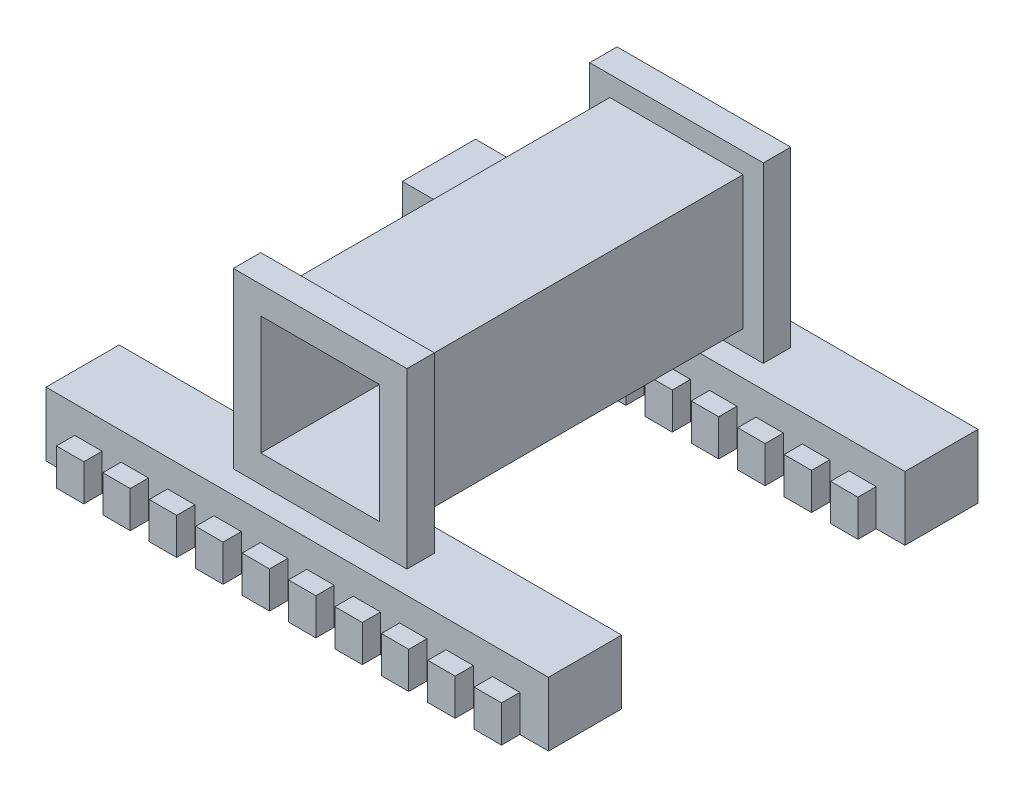
SolidWorks part; units mm, degrees
ref_plane "前视基准面" through (0, 0, 0) normal (0, 0, 1) x (1, 0, 0)
ref_plane "上视基准面" through (0, 0, 0) normal (0, 1, 0) x (1, 0, 0)
ref_plane "右视基准面" through (0, 0, 0) normal (1, 0, 0) x (0, 0, -1)
sketch "草图1" plane through (0, 0, 0) normal (0, 0, 1) x (1, 0, 0)
  line L0 (-9.5, 9.5) -> (9.5, 9.5)
  line L1 (-6.5, -6.5) -> (6.5, -6.5)
  line L2 (-6.5, -6.5) -> (-6.5, 6.5)
  line L3 (-6.5, 6.5) -> (6.5, 6.5)
  line L4 (6.5, -6.5) -> (6.5, 6.5)
  line L5 (-6.5, -6.5) -> (6.5, 6.5) construction
  line L6 (-6.5, 6.5) -> (6.5, -6.5) construction
  line L7 (9.5, -9.5) -> (9.5, 9.5)
  line L8 (-9.5, -9.5) -> (9.5, -9.5)
  line L9 (-9.5, -9.5) -> (-9.5, 9.5)
  line L10 (-7.3, 7.3) -> (7.3, 7.3)
  line L11 (7.3, -7.3) -> (7.3, 7.3)
  line L12 (-7.3, -7.3) -> (7.3, -7.3)
  line L13 (-7.3, -7.3) -> (-7.3, 7.3)
  line L15 (-27.5, -9.5) -> (27.5, -9.5)
  line L16 (-27.5, -9.5) -> (-27.5, -16.5)
  line L17 (-27.5, -16.5) -> (27.5, -16.5)
  line L18 (27.5, -9.5) -> (27.5, -16.5)
  point P0 (0, 0)
  dimension "D1" = 3
  dimension "D2" = 0.8
extrude "凸台-拉伸1" add sketch "草图1" along normal mid plane 42 contours L18 L15 L8 L16 L17 | L9 L8 L7 L0 L12 L13 L10 L11 | L13 L10 L11 L12 region at (0, 9.2313, 0) region at (0, -13, 0)
extrude "切除-拉伸1" cut sketch "草图1<3>" against normal mid plane 42 contours L2 L3 L4 L1
sketch "草图1<3>" plane through (0, 0, 0) normal (0, 0, 1) x (1, 0, 0) same geometry as "草图1"
sketch "草图2" plane through (0, 0, 0) normal (1, 0, 0) x (0, 0, -1)
  line L0 (21, -16.5) -> (21, -9.5) construction
  line L1 (21, -9.5) -> (-21, -9.5) construction
  line L2 (-21, -9.5) -> (-21, -16.5) construction
  line L3 (-21, -16.5) -> (21, -16.5) construction
  line L4 (21, -9.5) -> (21, 9.5) construction
  line L5 (21, 9.5) -> (-21, 9.5) construction
  line L6 (-21, 9.5) -> (-21, -9.5) construction
  line L7 (-21, -9.5) -> (21, -9.5) construction
  line L8 (21, -16.5) -> (21, -9.5)
  line L9 (21, -9.5) -> (-21, -9.5)
  line L10 (-21, -9.5) -> (-21, -16.5)
  line L11 (-21, -16.5) -> (21, -16.5)
  line L12 (21, -9.5) -> (21, 9.5)
  line L13 (21, 9.5) -> (-21, 9.5)
  line L14 (-21, 9.5) -> (-21, -9.5)
  line L15 (-21, -9.5) -> (21, -9.5)
extrude "切除-拉伸6" cut sketch "草图1<12>" against normal mid plane 36 contours L1 L4 L3 L2 | L9 L0 L7 L8 | L13 L10 L11 L12 region at (0, 0, 0)
sketch "草图1<12>" plane through (0, 0, 0) normal (0, 0, 1) x (1, 0, 0) same geometry as "草图1"
extrude "切除-拉伸7" cut sketch "草图1<13>" against normal mid plane 29 contours L18 L15 L8 L16 L17 region at (0, -13, 0)
sketch "草图1<13>" plane through (0, 0, 0) normal (0, 0, 1) x (1, 0, 0) same geometry as "草图1"
sketch "草图4" plane through (0, 0, 0) normal (1, 0, 0) x (0, 0, -1)
  line L0 (-21, -9.5) -> (-14.5, -9.5) construction
  line L1 (-14.5, -9.5) -> (-14.5, -16.5) construction
  line L2 (-14.5, -16.5) -> (-21, -16.5) construction
  line L3 (-21, -16.5) -> (-21, -9.5) construction
  line L4 (-18, 9.5) -> (-18, -9.5) construction
  line L5 (-18, -9.5) -> (-21, -9.5) construction
  line L6 (-21, -9.5) -> (-21, 9.5) construction
  line L7 (-21, 9.5) -> (-18, 9.5) construction
  line L8 (-18, -7.3) -> (-18, 7.3) construction
  line L9 (-18, 7.3) -> (18, 7.3) construction
  line L10 (18, 7.3) -> (18, -7.3) construction
  line L11 (18, -7.3) -> (-18, -7.3) construction
  line L12 (21, -9.5) -> (18, -9.5) construction
  line L13 (18, -9.5) -> (18, 9.5) construction
  line L14 (18, 9.5) -> (21, 9.5) construction
  line L15 (21, 9.5) -> (21, -9.5) construction
  line L16 (14.5, -16.5) -> (14.5, -9.5) construction
  line L17 (14.5, -9.5) -> (21, -9.5) construction
  line L18 (21, -9.5) -> (21, -16.5) construction
  line L19 (21, -16.5) -> (14.5, -16.5) construction
  line L20 (-21, -9.5) -> (-14.5, -9.5)
  line L21 (-14.5, -9.5) -> (-14.5, -16.5)
  line L22 (-14.5, -16.5) -> (-21, -16.5)
  line L23 (-21, -16.5) -> (-21, -9.5)
  line L24 (-18, 9.5) -> (-18, -9.5)
  line L25 (-18, -9.5) -> (-21, -9.5)
  line L26 (-21, -9.5) -> (-21, 9.5)
  line L27 (-21, 9.5) -> (-18, 9.5)
  line L28 (-18, -7.3) -> (-18, 7.3)
  line L29 (-18, 7.3) -> (18, 7.3)
  line L30 (18, 7.3) -> (18, -7.3)
  line L31 (18, -7.3) -> (-18, -7.3)
  line L32 (21, -9.5) -> (18, -9.5)
  line L33 (18, -9.5) -> (18, 9.5)
  line L34 (18, 9.5) -> (21, 9.5)
  line L35 (21, 9.5) -> (21, -9.5)
  line L36 (14.5, -16.5) -> (14.5, -9.5)
  line L37 (14.5, -9.5) -> (21, -9.5)
  line L38 (21, -9.5) -> (21, -16.5)
  line L39 (21, -16.5) -> (14.5, -16.5)
  line L40 (21, -9.5) -> (24.5, -9.5)
  line L41 (24.5, -9.5) -> (24.5, -16.5)
  line L42 (24.5, -16.5) -> (21, -16.5)
  line L43 (-21, -16.5) -> (-24.5049, -16.5)
  line L44 (-24.5049, -16.5) -> (-24.5049, -9.5)
  line L45 (-24.5049, -9.5) -> (-21, -9.5)
extrude "凸台-拉伸2" add sketch "草图4" along normal mid plane 55 contours L42 L41 L40 L38 | L45 L44 L43 L23 region at (0, -13, 22.7525) region at (0, -13, -22.75)
sketch "草图5" plane through (0, 0, -24.5) normal (0, 0, -1) x (-1, 0, 0)
  line L4 (27.5, -16.5) -> (27.5, -9.5)
  line L5 (27.5, -9.5) -> (-27.5, -9.5)
  line L6 (-27.5, -9.5) -> (-27.5, -16.5)
  line L7 (-27.5, -16.5) -> (27.5, -16.5)
  line L8 (27.5, -16.5) -> (27.5, -9.5)
  line L9 (27.5, -9.5) -> (-27.5, -9.5)
  line L10 (-27.5, -9.5) -> (-27.5, -16.5)
  line L12 (-9.5, -9.5) -> (9.5, -9.5)
  line L13 (-9.5, 9.5) -> (-9.5, -9.5)
  line L14 (9.5, 9.5) -> (-9.5, 9.5)
  line L15 (9.5, -9.5) -> (9.5, 9.5)
  line L16 (-9.5, -9.5) -> (9.5, -9.5)
  line L17 (-9.5, 9.5) -> (-9.5, -9.5)
  line L18 (9.5, 9.5) -> (-9.5, 9.5)
  line L19 (9.5, -9.5) -> (9.5, 9.5)
  line L24 (-27.5, -16.5) -> (27.5, -16.5) construction
  line L37 (22.8593, -16.5) -> (27.5, -16.5)
  line L50 (-21.36, -16.5) -> (-24.36, -16.5)
  line L55 (-11.187, -12.5036) -> (-14.213, -12.5036)
  line L56 (-11.187, -12.5036) -> (-11.187, -16.5)
  line L61 (-6.12, -16.5) -> (-9.12, -16.5)
  line L62 (-6.12, -16.5) -> (-6.12, -12.5036)
  line L68 (-1.04, -16.4978) -> (-4.04, -16.4978)
  line L86 (9.12, -16.5) -> (6.12, -16.5)
  line L91 (9.12, -16.5) -> (9.12, -12.5)
  line L92 (9.12, -12.5) -> (6.12, -12.5)
  line L97 (6.12, -16.5) -> (6.12, -12.5)
  line L98 (9.12, -16.5) -> (6.12, -12.5) construction
  line L103 (-21.36, -16.5) -> (-21.36, -12.5036)
  line L104 (-21.36, -12.5036) -> (-24.36, -12.5036)
  line L105 (-24.36, -16.5) -> (-24.36, -12.5036)
  line L106 (-21.36, -16.5) -> (-24.36, -12.5036) construction
  line L107 (-21.36, -12.5036) -> (-24.36, -16.5) construction
  line L108 (-19.28, -16.5) -> (-16.28, -16.5)
  line L109 (-19.28, -16.5) -> (-19.28, -12.5036)
  line L110 (-19.28, -12.5036) -> (-16.28, -12.5036)
  line L111 (-16.28, -16.5) -> (-16.28, -12.5036)
  line L112 (-19.28, -16.5) -> (-16.28, -12.5036) construction
  line L113 (-19.28, -12.5036) -> (-16.28, -16.5) construction
  line L114 (-11.187, -16.5) -> (-14.213, -16.5)
  line L115 (-14.213, -12.5036) -> (-14.213, -16.5)
  line L116 (-11.187, -12.5036) -> (-14.213, -16.5) construction
  line L117 (-11.187, -16.5) -> (-14.213, -12.5036) construction
  line L118 (-6.12, -12.5036) -> (-9.12, -12.5036)
  line L119 (-9.12, -16.5) -> (-9.12, -12.5036)
  line L120 (-6.12, -16.5) -> (-9.12, -12.5036) construction
  line L121 (-6.12, -12.5036) -> (-9.12, -16.5) construction
  line L122 (-1.04, -16.4978) -> (-1.04, -12.4978)
  line L123 (-1.04, -12.4978) -> (-4.04, -12.4978)
  line L124 (-4.04, -16.4978) -> (-4.04, -12.4978)
  line L125 (-1.04, -16.4978) -> (-4.04, -12.4978) construction
  line L126 (-1.04, -12.4978) -> (-4.04, -16.4978) construction
  line L128 (9.12, -12.5) -> (6.12, -16.5) construction
  line L129 (4.04, -16.5) -> (1.038, -16.5)
  line L130 (4.04, -16.5) -> (4.04, -12.4956)
  line L131 (4.04, -12.4956) -> (1.038, -12.4956)
  line L132 (1.038, -16.5) -> (1.038, -12.4956)
  line L133 (4.04, -16.5) -> (1.038, -12.4956) construction
  line L134 (4.04, -12.4956) -> (1.038, -16.5) construction
  line L135 (14.2014, -16.5) -> (11.1986, -16.5)
  line L136 (14.2014, -16.5) -> (14.2014, -12.5)
  line L137 (14.2014, -12.5) -> (11.1986, -12.5)
  line L138 (11.1986, -16.5) -> (11.1986, -12.5)
  line L139 (14.2014, -16.5) -> (11.1986, -12.5) construction
  line L140 (14.2014, -12.5) -> (11.1986, -16.5) construction
  line L141 (19.28, -16.4935) -> (16.28, -16.4935)
  line L142 (19.28, -16.4935) -> (19.28, -12.4935)
  line L143 (19.28, -12.4935) -> (16.28, -12.4935)
  line L144 (16.28, -16.4935) -> (16.28, -12.4935)
  line L145 (19.28, -16.4935) -> (16.28, -12.4935) construction
  line L146 (19.28, -12.4935) -> (16.28, -16.4935) construction
  line L151 (24.3586, -16.5) -> (21.36, -16.5)
  line L152 (24.3586, -16.5) -> (24.3586, -12.487)
  line L153 (24.3586, -12.487) -> (21.36, -12.487)
  line L154 (21.36, -16.5) -> (21.36, -12.487)
  line L155 (24.3586, -16.5) -> (21.36, -12.487) construction
  line L156 (24.3586, -12.487) -> (21.36, -16.5) construction
  point P6 (-22.86, -14.5018)
  point P33 (-17.78, -14.5018)
  point P35 (-17.78, -14.5018)
  point P39 (-12.7, -14.5018)
  point P40 (-12.7, -14.5018)
  point P45 (-7.62, -14.5018)
  point P50 (-2.54, -14.4978)
  point P55 (2.539, -14.4978)
  point P60 (7.62, -14.5)
  point P65 (12.7, -14.5)
  point P70 (17.78, -14.4935)
  point P75 (22.8593, -14.4935)
  dimension "D1" = 0
  dimension "D2" = 0
sketch "草图10" plane through (27.5, 0, 0) normal (1, 0, 0) x (0, 0, -1)
  line L0 (-24.5049, -16.5) -> (-25.5049, -16.5)
  line L1 (-24.5049, -16.5) -> (-24.5049, -9.5)
  line L2 (-24.5049, -9.5) -> (-25.5049, -9.5)
  line L3 (-25.5049, -9.5) -> (-25.5049, -16.5)
  line L4 (-14.5, -16.5) -> (-13.5, -16.5)
  line L5 (-13.5, -16.5) -> (-13.5, -9.5)
  line L6 (-13.5, -9.5) -> (-14.5, -9.5)
  line L7 (-14.5, -9.5) -> (-14.5, -16.5)
  line L8 (14.4975, -9.5) -> (14.4975, -16.5)
  line L11 (-0.0012, -16.5) -> (-0.0012, -9.5)
  line L12 (13.4975, -9.5) -> (14.4975, -9.5)
  line L13 (13.4975, -16.5) -> (13.4975, -9.5)
  line L14 (14.4975, -16.5) -> (13.4975, -16.5)
  line L15 (25.5025, -9.5) -> (25.5025, -16.5)
  line L16 (24.5025, -9.5) -> (25.5025, -9.5)
  line L17 (24.5025, -16.5) -> (24.5025, -9.5)
  line L18 (24.5025, -16.5) -> (25.5025, -16.5)
extrude "凸台-拉伸4" add sketch "草图10" against normal blind 55 contours L7 L4 L5 L6 | L3 L0 L1 L2
sketch "草图14" plane through (27.5, 0, 0) normal (1, 0, 0) x (0, 0, -1)
  line L0 (14.5, -9.5) -> (13.5, -9.5)
  line L1 (14.5, -16.5) -> (13.5, -16.5)
  line L2 (13.5, -16.5) -> (13.5, -9.5)
  line L3 (24.5, -9.5) -> (25.5, -9.5)
  line L4 (24.5, -16.5) -> (25.5, -16.5)
  line L5 (25.5, -16.5) -> (25.5, -9.5)
  line L6 (24.5, -9.5) -> (24.5, -16.5)
  line L7 (14.5, -9.5) -> (14.5, -16.5)
extrude "凸台-拉伸6" add sketch "草图14" against normal blind 55
sketch "草图15" plane through (0, 0, -25.5) normal (0, 0, -1) x (-1, 0, 0)
  line L0 (-27.5, -16.5) -> (-22.86, -16.5)
  line L1 (27.5, -16.5) -> (-27.5, -16.5) construction
  line L2 (-22.86, -16.5) -> (-22.86, -12.5)
  line L4 (-17.78, -12.5) -> (-17.78, -16.5)
  line L5 (-11.2, -16.5) -> (-14.2, -16.5)
  line L6 (-12.7, -16.5) -> (-12.7, -12.5)
  line L7 (-11.2, -16.5) -> (-11.2, -12.5)
  line L8 (-7.62, -12.5) -> (-7.62, -16.5)
  line L9 (-11.2, -12.5) -> (-14.2, -12.5)
  line L10 (-2.54, -16.5) -> (-2.54, -12.5)
  line L11 (-1.04, -16.5) -> (-4.04, -16.5)
  line L12 (2.54, -12.5) -> (2.54, -16.5)
  line L13 (-1.04, -16.5) -> (-1.04, -12.5)
  line L14 (7.62, -16.5) -> (7.62, -12.5)
  line L15 (6.12, -16.5) -> (9.12, -16.5)
  line L16 (12.7, -12.5) -> (12.7, -16.5)
  line L17 (6.12, -16.5) -> (6.12, -12.5)
  line L18 (17.78, -16.5) -> (17.78, -12.5)
  line L19 (6.12, -12.5) -> (9.12, -12.5)
  line L20 (22.86, -12.5) -> (22.86, -16.5)
  line L21 (24.36, -16.5) -> (21.36, -16.5)
  line L31 (24.36, -16.5) -> (24.36, -12.5)
  line L32 (24.36, -12.5) -> (21.36, -12.5)
  line L37 (9.12, -16.5) -> (9.12, -12.5)
  line L38 (6.12, -16.5) -> (9.12, -12.5) construction
  line L39 (-19.28, -16.5) -> (-16.28, -16.5)
  line L48 (-21.36, -16.5) -> (-24.36, -16.5)
  line L49 (-21.36, -16.5) -> (-21.36, -12.5)
  line L50 (-21.36, -12.5) -> (-24.36, -12.5)
  line L51 (-24.36, -16.5) -> (-24.36, -12.5)
  line L52 (-21.36, -16.5) -> (-24.36, -12.5) construction
  line L53 (-21.36, -12.5) -> (-24.36, -16.5) construction
  line L58 (-19.28, -16.5) -> (-19.28, -12.5)
  line L59 (-19.28, -12.5) -> (-16.28, -12.5)
  line L60 (-16.28, -16.5) -> (-16.28, -12.5)
  line L61 (-19.28, -16.5) -> (-16.28, -12.5) construction
  line L62 (-19.28, -12.5) -> (-16.28, -16.5) construction
  line L67 (-14.2, -16.5) -> (-14.2, -12.5)
  line L68 (-11.2, -16.5) -> (-14.2, -12.5) construction
  line L69 (-11.2, -12.5) -> (-14.2, -16.5) construction
  line L70 (-9.12, -16.5) -> (-6.12, -16.5)
  line L71 (-9.12, -16.5) -> (-9.12, -12.5)
  line L72 (-9.12, -12.5) -> (-6.12, -12.5)
  line L73 (-6.12, -16.5) -> (-6.12, -12.5)
  line L74 (-9.12, -16.5) -> (-6.12, -12.5) construction
  line L75 (-9.12, -12.5) -> (-6.12, -16.5) construction
  line L76 (-1.04, -12.5) -> (-4.04, -12.5)
  line L77 (-4.04, -16.5) -> (-4.04, -12.5)
  line L78 (-1.04, -16.5) -> (-4.04, -12.5) construction
  line L79 (-1.04, -12.5) -> (-4.04, -16.5) construction
  line L80 (4.04, -16.5) -> (1.04, -16.5)
  line L81 (4.04, -16.5) -> (4.04, -12.5)
  line L82 (4.04, -12.5) -> (1.04, -12.5)
  line L83 (1.04, -16.5) -> (1.04, -12.5)
  line L84 (4.04, -16.5) -> (1.04, -12.5) construction
  line L85 (4.04, -12.5) -> (1.04, -16.5) construction
  line L86 (6.12, -12.5) -> (9.12, -16.5) construction
  line L87 (11.2, -16.5) -> (14.2, -16.5)
  line L88 (11.2, -16.5) -> (11.2, -12.5)
  line L89 (11.2, -12.5) -> (14.2, -12.5)
  line L90 (14.2, -16.5) -> (14.2, -12.5)
  line L91 (11.2, -16.5) -> (14.2, -12.5) construction
  line L92 (11.2, -12.5) -> (14.2, -16.5) construction
  line L93 (16.28, -16.5) -> (19.28, -16.5)
  line L94 (16.28, -16.5) -> (16.28, -12.5)
  line L95 (16.28, -12.5) -> (19.28, -12.5)
  line L96 (19.28, -16.5) -> (19.28, -12.5)
  line L97 (16.28, -16.5) -> (19.28, -12.5) construction
  line L98 (16.28, -12.5) -> (19.28, -16.5) construction
  line L99 (21.36, -16.5) -> (21.36, -12.5)
  line L100 (24.36, -16.5) -> (21.36, -12.5) construction
  line L101 (24.36, -12.5) -> (21.36, -16.5) construction
  point P17 (22.86, -14.5)
  point P25 (22.86, -14.5)
  point P26 (22.86, -14.5)
  point P31 (17.78, -14.5)
  point P32 (7.62, -14.5)
  point P36 (-22.86, -14.5)
  point P41 (-17.78, -14.5)
  point P42 (-17.78, -14.5)
  point P47 (-12.7, -14.5)
  point P52 (-7.62, -14.5)
  point P57 (-2.54, -14.5)
  point P62 (2.54, -14.5)
  point P68 (12.7, -14.5)
  point P73 (17.78, -14.5)
  line M64 (-27.5, -9.5) -> (-27.5, -16.5)
  line M65 (-27.5, -16.5) -> (27.5, -16.5)
  line M66 (27.5, -16.5) -> (27.5, -9.5)
  line M67 (27.5, -9.5) -> (-27.5, -9.5)
extrude "切除-拉伸22" cut sketch "草图15" against normal blind 2 contours L99 L32 L31 L51 L50 L49 L58 L59 L60 L67 L9 L7 L71 L72 L73 L77 L76 L13 L83 L82 L81 L17 L19 L37 L88 L89 L90 L94 M65 M66 M67 M64 region at (0, -12.3208, -25.5)
sketch "草图20" plane through (0, 0, 13.5) normal (0, 0, -1) x (-1, 0, 0)
  line L0 (21.36, -16.5) -> (24.36, -16.5) construction
  line L1 (24.36, -16.5) -> (24.36, -12.5) construction
  line L2 (24.36, -12.5) -> (21.36, -12.5) construction
  line L3 (21.36, -12.5) -> (21.36, -16.5) construction
  line L4 (-27.5, -9.5) -> (-27.5, -16.5)
  line L5 (-27.5, -16.5) -> (27.5, -16.5)
  line L6 (27.5, -16.5) -> (27.5, -9.5)
  line L7 (27.5, -9.5) -> (-27.5, -9.5)
  line L8 (-27.5, -9.5) -> (-27.5, -16.5)
  line L9 (-27.5, -16.5) -> (27.5, -16.5)
  line L10 (27.5, -16.5) -> (27.5, -9.5)
  line L11 (27.5, -9.5) -> (-27.5, -9.5)
  line L12 (16.28, -16.5) -> (19.28, -16.5) construction
  line L13 (19.28, -16.5) -> (19.28, -12.5) construction
  line L14 (19.28, -12.5) -> (16.28, -12.5) construction
  line L15 (16.28, -12.5) -> (16.28, -16.5) construction
  line L16 (11.2, -16.5) -> (14.2, -16.5) construction
  line L17 (14.2, -16.5) -> (14.2, -12.5) construction
  line L18 (14.2, -12.5) -> (11.2, -12.5) construction
  line L19 (11.2, -12.5) -> (11.2, -16.5) construction
  line L20 (6.12, -16.5) -> (9.12, -16.5) construction
  line L21 (9.12, -16.5) -> (9.12, -12.5) construction
  line L22 (9.12, -12.5) -> (6.12, -12.5) construction
  line L23 (6.12, -12.5) -> (6.12, -16.5) construction
  line L24 (1.04, -16.5) -> (4.04, -16.5) construction
  line L25 (4.04, -16.5) -> (4.04, -12.5) construction
  line L26 (4.04, -12.5) -> (1.04, -12.5) construction
  line L27 (1.04, -12.5) -> (1.04, -16.5) construction
  line L28 (-4.04, -16.5) -> (-1.04, -16.5) construction
  line L29 (-1.04, -16.5) -> (-1.04, -12.5) construction
  line L30 (-1.04, -12.5) -> (-4.04, -12.5) construction
  line L31 (-4.04, -12.5) -> (-4.04, -16.5) construction
  line L32 (-9.12, -16.5) -> (-6.12, -16.5) construction
  line L33 (-6.12, -16.5) -> (-6.12, -12.5) construction
  line L34 (-6.12, -12.5) -> (-9.12, -12.5) construction
  line L35 (-9.12, -12.5) -> (-9.12, -16.5) construction
  line L36 (-14.2, -16.5) -> (-11.2, -16.5) construction
  line L37 (-11.2, -16.5) -> (-11.2, -12.5) construction
  line L38 (-11.2, -12.5) -> (-14.2, -12.5) construction
  line L39 (-14.2, -12.5) -> (-14.2, -16.5) construction
  line L40 (-19.28, -16.5) -> (-16.28, -16.5) construction
  line L41 (-16.28, -16.5) -> (-16.28, -12.5) construction
  line L42 (-16.28, -12.5) -> (-19.28, -12.5) construction
  line L43 (-19.28, -12.5) -> (-19.28, -16.5) construction
  line L44 (-24.36, -16.5) -> (-21.36, -16.5) construction
  line L45 (-21.36, -16.5) -> (-21.36, -12.5) construction
  line L46 (-21.36, -12.5) -> (-24.36, -12.5) construction
  line L47 (-24.36, -12.5) -> (-24.36, -16.5) construction
  line L48 (21.36, -16.5) -> (24.36, -16.5)
  line L49 (24.36, -16.5) -> (24.36, -12.5)
  line L50 (24.36, -12.5) -> (21.36, -12.5)
  line L51 (21.36, -12.5) -> (21.36, -16.5)
  line L52 (16.28, -16.5) -> (19.28, -16.5)
  line L53 (19.28, -16.5) -> (19.28, -12.5)
  line L54 (19.28, -12.5) -> (16.28, -12.5)
  line L55 (16.28, -12.5) -> (16.28, -16.5)
  line L56 (11.2, -16.5) -> (14.2, -16.5)
  line L57 (14.2, -16.5) -> (14.2, -12.5)
  line L58 (14.2, -12.5) -> (11.2, -12.5)
  line L59 (11.2, -12.5) -> (11.2, -16.5)
  line L60 (6.12, -16.5) -> (9.12, -16.5)
  line L61 (9.12, -16.5) -> (9.12, -12.5)
  line L62 (9.12, -12.5) -> (6.12, -12.5)
  line L63 (6.12, -12.5) -> (6.12, -16.5)
  line L64 (1.04, -16.5) -> (4.04, -16.5)
  line L65 (4.04, -16.5) -> (4.04, -12.5)
  line L66 (4.04, -12.5) -> (1.04, -12.5)
  line L67 (1.04, -12.5) -> (1.04, -16.5)
  line L68 (-4.04, -16.5) -> (-1.04, -16.5)
  line L69 (-1.04, -16.5) -> (-1.04, -12.5)
  line L70 (-1.04, -12.5) -> (-4.04, -12.5)
  line L71 (-4.04, -12.5) -> (-4.04, -16.5)
  line L72 (-9.12, -16.5) -> (-6.12, -16.5)
  line L73 (-6.12, -16.5) -> (-6.12, -12.5)
  line L74 (-6.12, -12.5) -> (-9.12, -12.5)
  line L75 (-9.12, -12.5) -> (-9.12, -16.5)
  line L76 (-14.2, -16.5) -> (-11.2, -16.5)
  line L77 (-11.2, -16.5) -> (-11.2, -12.5)
  line L78 (-11.2, -12.5) -> (-14.2, -12.5)
  line L79 (-14.2, -12.5) -> (-14.2, -16.5)
  line L80 (-19.28, -16.5) -> (-16.28, -16.5)
  line L81 (-16.28, -16.5) -> (-16.28, -12.5)
  line L82 (-16.28, -12.5) -> (-19.28, -12.5)
  line L83 (-19.28, -12.5) -> (-19.28, -16.5)
  line L84 (-24.36, -16.5) -> (-21.36, -16.5)
  line L85 (-21.36, -16.5) -> (-21.36, -12.5)
  line L86 (-21.36, -12.5) -> (-24.36, -12.5)
  line L87 (-24.36, -12.5) -> (-24.36, -16.5)
  line M5 (-27.5, -9.5) -> (-27.5, -16.5)
  line M6 (-27.5, -16.5) -> (27.5, -16.5)
  line M7 (27.5, -16.5) -> (27.5, -9.5)
  line M8 (27.5, -9.5) -> (-27.5, -9.5)
  dimension "D1" = 0
extrude "切除-拉伸23" cut sketch "草图20" against normal blind 2 contours L87 L86 L85 L83 L82 L81 L79 L78 L77 L75 L74 L73 L71 L70 L69 L67 L66 L65 L63 L62 L61 L59 L58 L57 L55 L54 L53 L51 L50 L49 M6 M7 M8 M5 region at (0, -12.3208, 13.5)
sketch "草图21" plane through (0, 0, -13.5) normal (0, 0, 1) x (1, 0, 0)
  line L0 (-21.36, -16.5) -> (-24.36, -16.5) construction
  line L1 (-24.36, -16.5) -> (-24.36, -12.5) construction
  line L2 (-24.36, -12.5) -> (-21.36, -12.5) construction
  line L3 (-21.36, -12.5) -> (-21.36, -16.5) construction
  line L4 (27.5, -16.5) -> (27.5, -9.5)
  line L5 (27.5, -9.5) -> (-27.5, -9.5)
  line L6 (-27.5, -9.5) -> (-27.5, -16.5)
  line L7 (-27.5, -16.5) -> (27.5, -16.5)
  line L8 (27.5, -16.5) -> (27.5, -9.5)
  line L9 (27.5, -9.5) -> (-27.5, -9.5)
  line L10 (-27.5, -9.5) -> (-27.5, -16.5)
  line L11 (-27.5, -16.5) -> (27.5, -16.5)
  line L12 (-16.28, -16.5) -> (-19.28, -16.5) construction
  line L13 (-19.28, -16.5) -> (-19.28, -12.5) construction
  line L14 (-19.28, -12.5) -> (-16.28, -12.5) construction
  line L15 (-16.28, -12.5) -> (-16.28, -16.5) construction
  line L16 (-11.2, -16.5) -> (-14.2, -16.5) construction
  line L17 (-14.2, -16.5) -> (-14.2, -12.5) construction
  line L18 (-14.2, -12.5) -> (-11.2, -12.5) construction
  line L19 (-11.2, -12.5) -> (-11.2, -16.5) construction
  line L20 (-6.12, -16.5) -> (-9.12, -16.5) construction
  line L21 (-9.12, -16.5) -> (-9.12, -12.5) construction
  line L22 (-9.12, -12.5) -> (-6.12, -12.5) construction
  line L23 (-6.12, -12.5) -> (-6.12, -16.5) construction
  line L24 (-1.04, -16.5) -> (-4.04, -16.5) construction
  line L25 (-4.04, -16.5) -> (-4.04, -12.5) construction
  line L26 (-4.04, -12.5) -> (-1.04, -12.5) construction
  line L27 (-1.04, -12.5) -> (-1.04, -16.5) construction
  line L28 (4.04, -16.5) -> (1.04, -16.5) construction
  line L29 (1.04, -16.5) -> (1.04, -12.5) construction
  line L30 (1.04, -12.5) -> (4.04, -12.5) construction
  line L31 (4.04, -12.5) -> (4.04, -16.5) construction
  line L32 (9.12, -16.5) -> (6.12, -16.5) construction
  line L33 (6.12, -16.5) -> (6.12, -12.5) construction
  line L34 (6.12, -12.5) -> (9.12, -12.5) construction
  line L35 (9.12, -12.5) -> (9.12, -16.5) construction
  line L36 (21.36, -12.5) -> (24.36, -12.5) construction
  line L37 (24.36, -12.5) -> (24.36, -16.5) construction
  line L38 (24.36, -16.5) -> (21.36, -16.5) construction
  line L39 (21.36, -16.5) -> (21.36, -12.5) construction
  line L40 (14.2, -16.5) -> (11.2, -16.5) construction
  line L41 (11.2, -16.5) -> (11.2, -12.5) construction
  line L42 (11.2, -12.5) -> (14.2, -12.5) construction
  line L43 (14.2, -12.5) -> (14.2, -16.5) construction
  line L44 (19.28, -16.5) -> (16.28, -16.5) construction
  line L45 (16.28, -16.5) -> (16.28, -12.5) construction
  line L46 (16.28, -12.5) -> (19.28, -12.5) construction
  line L47 (19.28, -12.5) -> (19.28, -16.5) construction
  line L48 (-21.36, -16.5) -> (-24.36, -16.5)
  line L49 (-24.36, -16.5) -> (-24.36, -12.5)
  line L50 (-24.36, -12.5) -> (-21.36, -12.5)
  line L51 (-21.36, -12.5) -> (-21.36, -16.5)
  line L52 (-16.28, -16.5) -> (-19.28, -16.5)
  line L53 (-19.28, -16.5) -> (-19.28, -12.5)
  line L54 (-19.28, -12.5) -> (-16.28, -12.5)
  line L55 (-16.28, -12.5) -> (-16.28, -16.5)
  line L56 (-11.2, -16.5) -> (-14.2, -16.5)
  line L57 (-14.2, -16.5) -> (-14.2, -12.5)
  line L58 (-14.2, -12.5) -> (-11.2, -12.5)
  line L59 (-11.2, -12.5) -> (-11.2, -16.5)
  line L60 (-6.12, -16.5) -> (-9.12, -16.5)
  line L61 (-9.12, -16.5) -> (-9.12, -12.5)
  line L62 (-9.12, -12.5) -> (-6.12, -12.5)
  line L63 (-6.12, -12.5) -> (-6.12, -16.5)
  line L64 (-1.04, -16.5) -> (-4.04, -16.5)
  line L65 (-4.04, -16.5) -> (-4.04, -12.5)
  line L66 (-4.04, -12.5) -> (-1.04, -12.5)
  line L67 (-1.04, -12.5) -> (-1.04, -16.5)
  line L68 (4.04, -16.5) -> (1.04, -16.5)
  line L69 (1.04, -16.5) -> (1.04, -12.5)
  line L70 (1.04, -12.5) -> (4.04, -12.5)
  line L71 (4.04, -12.5) -> (4.04, -16.5)
  line L72 (9.12, -16.5) -> (6.12, -16.5)
  line L73 (6.12, -16.5) -> (6.12, -12.5)
  line L74 (6.12, -12.5) -> (9.12, -12.5)
  line L75 (9.12, -12.5) -> (9.12, -16.5)
  line L76 (21.36, -12.5) -> (24.36, -12.5)
  line L77 (24.36, -12.5) -> (24.36, -16.5)
  line L78 (24.36, -16.5) -> (21.36, -16.5)
  line L79 (21.36, -16.5) -> (21.36, -12.5)
  line L80 (14.2, -16.5) -> (11.2, -16.5)
  line L81 (11.2, -16.5) -> (11.2, -12.5)
  line L82 (11.2, -12.5) -> (14.2, -12.5)
  line L83 (14.2, -12.5) -> (14.2, -16.5)
  line L84 (19.28, -16.5) -> (16.28, -16.5)
  line L85 (16.28, -16.5) -> (16.28, -12.5)
  line L86 (16.28, -12.5) -> (19.28, -12.5)
  line L87 (19.28, -12.5) -> (19.28, -16.5)
  line M5 (27.5, -16.5) -> (27.5, -9.5)
  line M6 (27.5, -9.5) -> (-27.5, -9.5)
  line M7 (-27.5, -9.5) -> (-27.5, -16.5)
  line M8 (-27.5, -16.5) -> (27.5, -16.5)
  dimension "D1" = 0
extrude "切除-拉伸24" cut sketch "草图21" against normal blind 2 contours L86 L87 L79 L76 L77 L11 L49 L50 L51 L53 L54 L55 L57 L58 L59 L61 L62 L63 L65 L66 L67 L69 L70 L71 L73 L74 L75 L81 L82 L83 L85 M8 M5 M6 M7 region at (0, -12.3208, -13.5)
sketch "草图22" plane through (0, 0, 25.5049) normal (0, 0, 1) x (1, 0, 0)
  line L0 (9.12, -16.5) -> (6.12, -16.5) construction
  line L1 (6.12, -16.5) -> (6.12, -12.5) construction
  line L2 (6.12, -12.5) -> (9.12, -12.5) construction
  line L3 (9.12, -12.5) -> (9.12, -16.5) construction
  line L4 (27.5, -16.5) -> (27.5, -9.5)
  line L5 (27.5, -9.5) -> (-27.5, -9.5)
  line L6 (-27.5, -9.5) -> (-27.5, -16.5)
  line L7 (-27.5, -16.5) -> (27.5, -16.5)
  line L8 (27.5, -16.5) -> (27.5, -9.5)
  line L9 (27.5, -9.5) -> (-27.5, -9.5)
  line L10 (-27.5, -9.5) -> (-27.5, -16.5)
  line L11 (-27.5, -16.5) -> (27.5, -16.5)
  line L12 (14.2, -16.5) -> (11.2, -16.5) construction
  line L13 (11.2, -16.5) -> (11.2, -12.5) construction
  line L14 (11.2, -12.5) -> (14.2, -12.5) construction
  line L15 (14.2, -12.5) -> (14.2, -16.5) construction
  line L16 (19.28, -16.5) -> (16.28, -16.5) construction
  line L17 (16.28, -16.5) -> (16.28, -12.5) construction
  line L18 (16.28, -12.5) -> (19.28, -12.5) construction
  line L19 (19.28, -12.5) -> (19.28, -16.5) construction
  line L20 (21.36, -12.5) -> (24.36, -12.5) construction
  line L21 (24.36, -12.5) -> (24.36, -16.5) construction
  line L22 (24.36, -16.5) -> (21.36, -16.5) construction
  line L23 (21.36, -16.5) -> (21.36, -12.5) construction
  line L24 (4.04, -16.5) -> (1.04, -16.5) construction
  line L25 (1.04, -16.5) -> (1.04, -12.5) construction
  line L26 (1.04, -12.5) -> (4.04, -12.5) construction
  line L27 (4.04, -12.5) -> (4.04, -16.5) construction
  line L28 (-1.04, -16.5) -> (-4.04, -16.5) construction
  line L29 (-4.04, -16.5) -> (-4.04, -12.5) construction
  line L30 (-4.04, -12.5) -> (-1.04, -12.5) construction
  line L31 (-1.04, -12.5) -> (-1.04, -16.5) construction
  line L32 (-6.12, -16.5) -> (-9.12, -16.5) construction
  line L33 (-9.12, -16.5) -> (-9.12, -12.5) construction
  line L34 (-9.12, -12.5) -> (-6.12, -12.5) construction
  line L35 (-6.12, -12.5) -> (-6.12, -16.5) construction
  line L36 (-11.2, -16.5) -> (-14.2, -16.5) construction
  line L37 (-14.2, -16.5) -> (-14.2, -12.5) construction
  line L38 (-14.2, -12.5) -> (-11.2, -12.5) construction
  line L39 (-11.2, -12.5) -> (-11.2, -16.5) construction
  line L40 (-16.28, -16.5) -> (-19.28, -16.5) construction
  line L41 (-19.28, -16.5) -> (-19.28, -12.5) construction
  line L42 (-19.28, -12.5) -> (-16.28, -12.5) construction
  line L43 (-16.28, -12.5) -> (-16.28, -16.5) construction
  line L44 (-21.36, -16.5) -> (-24.36, -16.5) construction
  line L45 (-24.36, -16.5) -> (-24.36, -12.5) construction
  line L46 (-24.36, -12.5) -> (-21.36, -12.5) construction
  line L47 (-21.36, -12.5) -> (-21.36, -16.5) construction
  line L48 (9.12, -16.5) -> (6.12, -16.5)
  line L49 (6.12, -16.5) -> (6.12, -12.5)
  line L50 (6.12, -12.5) -> (9.12, -12.5)
  line L51 (9.12, -12.5) -> (9.12, -16.5)
  line L52 (14.2, -16.5) -> (11.2, -16.5)
  line L53 (11.2, -16.5) -> (11.2, -12.5)
  line L54 (11.2, -12.5) -> (14.2, -12.5)
  line L55 (14.2, -12.5) -> (14.2, -16.5)
  line L56 (19.28, -16.5) -> (16.28, -16.5)
  line L57 (16.28, -16.5) -> (16.28, -12.5)
  line L58 (16.28, -12.5) -> (19.28, -12.5)
  line L59 (19.28, -12.5) -> (19.28, -16.5)
  line L60 (21.36, -12.5) -> (24.36, -12.5)
  line L61 (24.36, -12.5) -> (24.36, -16.5)
  line L62 (24.36, -16.5) -> (21.36, -16.5)
  line L63 (21.36, -16.5) -> (21.36, -12.5)
  line L64 (4.04, -16.5) -> (1.04, -16.5)
  line L65 (1.04, -16.5) -> (1.04, -12.5)
  line L66 (1.04, -12.5) -> (4.04, -12.5)
  line L67 (4.04, -12.5) -> (4.04, -16.5)
  line L68 (-1.04, -16.5) -> (-4.04, -16.5)
  line L69 (-4.04, -16.5) -> (-4.04, -12.5)
  line L70 (-4.04, -12.5) -> (-1.04, -12.5)
  line L71 (-1.04, -12.5) -> (-1.04, -16.5)
  line L72 (-6.12, -16.5) -> (-9.12, -16.5)
  line L73 (-9.12, -16.5) -> (-9.12, -12.5)
  line L74 (-9.12, -12.5) -> (-6.12, -12.5)
  line L75 (-6.12, -12.5) -> (-6.12, -16.5)
  line L76 (-11.2, -16.5) -> (-14.2, -16.5)
  line L77 (-14.2, -16.5) -> (-14.2, -12.5)
  line L78 (-14.2, -12.5) -> (-11.2, -12.5)
  line L79 (-11.2, -12.5) -> (-11.2, -16.5)
  line L80 (-16.28, -16.5) -> (-19.28, -16.5)
  line L81 (-19.28, -16.5) -> (-19.28, -12.5)
  line L82 (-19.28, -12.5) -> (-16.28, -12.5)
  line L83 (-16.28, -12.5) -> (-16.28, -16.5)
  line L84 (-21.36, -16.5) -> (-24.36, -16.5)
  line L85 (-24.36, -16.5) -> (-24.36, -12.5)
  line L86 (-24.36, -12.5) -> (-21.36, -12.5)
  line L87 (-21.36, -12.5) -> (-21.36, -16.5)
  line M5 (27.5, -16.5) -> (27.5, -9.5)
  line M6 (27.5, -9.5) -> (-27.5, -9.5)
  line M7 (-27.5, -9.5) -> (-27.5, -16.5)
  line M8 (-27.5, -16.5) -> (27.5, -16.5)
  dimension "D1" = 0
extrude "切除-拉伸25" cut sketch "草图22" against normal blind 2 contours L86 L87 L81 L82 L83 L77 L78 L79 L73 L74 L75 L69 L70 L71 L65 L66 L67 L49 L50 L51 L53 L54 L55 L57 L58 L59 L63 L60 L61 L11 L85 M8 M5 M6 M7 region at (0, -12.3208, 25.5049)
sketch "草图23" plane through (0, -16.5, 0) normal (0, -1, 0) x (1, 0, 0)
  line L2 (21.36, 13.5) -> (24.36, 13.5) construction
  line L5 (-24.36, 13.5) -> (-21.36, 13.5) construction
  line L7 (24.86, 16.5025) -> (24.86, 22.5025)
  line L9 (-24.86, 19.5025) -> (-24.86, 22.5025)
  line L10 (-24.86, 22.5025) -> (24.86, 22.5025)
  line L11 (24.86, 16.5025) -> (-24.86, 16.5025)
  line L12 (-24.86, 16.5025) -> (-24.86, 19.5025)
  line L13 (-22.86, 13.5) -> (-22.86, -13.5)
  line L14 (-24.36, -13.5) -> (-21.36, -13.5) construction
  line L15 (22.86, 13.5) -> (22.86, -13.5)
  line L16 (21.36, -13.5) -> (24.36, -13.5) construction
  line L17 (22.86, 0) -> (-22.86, 0)
  line L18 (-24.86, -16.5025) -> (-24.86, -19.5025)
  line L19 (24.86, -16.5025) -> (-24.86, -16.5025)
  line L20 (24.86, -16.5025) -> (24.86, -22.5025)
  line L21 (-24.86, -22.5025) -> (24.86, -22.5025)
  line L22 (-24.86, -19.5025) -> (-24.86, -22.5025)
extrude "切除-拉伸26" cut sketch "草图23" against normal blind 4 contours L12 L11 L7 L10 L9 | L18 L22 L21 L20 L19 region at (0, -16.5, 19.5025) region at (0, -16.5, -19.5025)
